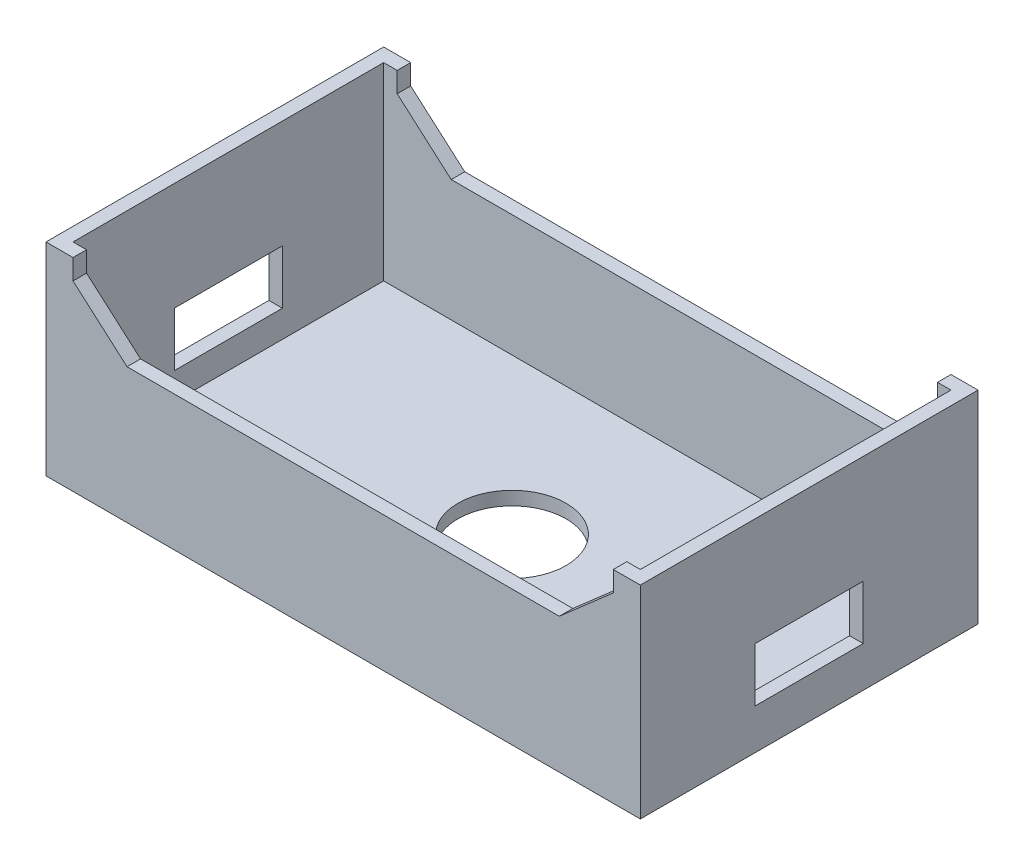
SolidWorks part; units mm, degrees
material "ABS"
ref_plane "Alzado" through (0, 0, 0) normal (0, 0, 1) x (1, 0, 0)
ref_plane "Planta" through (0, 0, 0) normal (0, 1, 0) x (1, 0, 0)
ref_plane "Vista lateral" through (0, 0, 0) normal (1, 0, 0) x (0, 0, -1)
sketch "Croquis1" plane through (0, 0, 0) normal (0, 1, 0) x (1, 0, 0)
  line L1 (22, -12.5) -> (-22, -12.5)
  line L2 (22, -12.5) -> (22, 12.5)
  line L3 (22, 12.5) -> (-22, 12.5)
  line L4 (-22, -12.5) -> (-22, 12.5)
  line L5 (22, -12.5) -> (-22, 12.5) construction
  line L6 (22, 12.5) -> (-22, -12.5) construction
  point P0 (0, 0)
  dimension "D1" = 25
  dimension "D2" = 44
extrude "Saliente-Extruir2" add sketch "Croquis1" along normal blind 10
sketch "Croquis2" plane through (0, 10, 0) normal (0, 1, 0) x (1, 0, 0)
  line L0 (22, 12.5) -> (-22, 12.5) construction
  line L1 (21, -11.5) -> (-21, -11.5)
  line L2 (21, -11.5) -> (21, 11.5)
  line L3 (21, 11.5) -> (-21, 11.5)
  line L4 (-21, -11.5) -> (-21, 11.5)
  line L5 (21, -11.5) -> (-21, 11.5) construction
  line L6 (21, 11.5) -> (-21, -11.5) construction
  line L7 (-22, 12.5) -> (-22, -12.5) construction
  point P0 (0, 0)
  dimension "D1" = 1
  dimension "D2" = 1
extrude "Cortar-Extruir1" cut sketch "Croquis2" against normal blind 9
sketch "Croquis3" plane through (0, 0, 12.5) normal (0, 0, 1) x (1, 0, 0)
  line L0 (0, 10) -> (0, 15.8262)
  line L1 (-22, 10) -> (22, 10) construction
  line L2 (-22, 10) -> (-23, 10)
  line L3 (-22, 10) -> (-22, 0) construction
  line L4 (-23, 10) -> (-23, 15)
  line L5 (-23, 15) -> (-20, 15)
  line L6 (-20, 15) -> (-20, 13.5)
  line L7 (-23, 10) -> (-16, 10)
  line L8 (-16, 10) -> (-20, 13.5)
  line L9 (16, 10) -> (20, 13.5)
  line L10 (23, 10) -> (16, 10)
  line L11 (20, 15) -> (20, 13.5)
  line L12 (23, 10) -> (23, 15)
  line L13 (22, 10) -> (23, 10)
  line L14 (-23, 10) -> (-23, 8)
  line L15 (-23, 8) -> (-22, 8)
  line L16 (-22, 8) -> (-22, 10)
  line L17 (22, 8) -> (22, 10)
  line L18 (23, 8) -> (22, 8)
  line L19 (23, 10) -> (23, 8)
  line L20 (22, 10) -> (23, 10)
  line L21 (20, 15) -> (23, 15)
  line M2 (22, 0) -> (22, 10)
  line M3 (22, 10) -> (-22, 10)
  line M4 (-22, 10) -> (-22, 0)
extrude "Saliente-Extruir3" add sketch "Croquis3" against normal blind 25 contours L8 L6 L5 L4 L2 M3 | L21 L11 L9 L10 L12 M3 | L14 L15 L2 M4 | L19 L10 L18 M2 region at (-22.5, 9, 12.5) region at (-20.5985, 12.0758, 12.5) region at (20.5985, 12.0758, 12.5) region at (22.5, 9, 12.5)
sketch "Croquis4" plane through (0, 1, 0) normal (0, 1, 0) x (1, 0, 0)
  line L0 (21, 11.5) -> (-21, 11.5) construction
  line L1 (21, -11.5) -> (-21, -11.5)
  line L2 (21, -11.5) -> (21, 11.5)
  line L3 (21, 11.5) -> (-21, 11.5)
  line L4 (-21, -11.5) -> (-21, 11.5)
  line L5 (21, -11.5) -> (-21, 11.5) construction
  line L6 (21, 11.5) -> (-21, -11.5) construction
  point P0 (0, 0)
extrude "Cortar-Extruir2" cut sketch "Croquis4" along normal blind 28
sketch "Croquis5" plane through (0, 15, 0) normal (0, 1, 0) x (1, 0, 0)
  line L0 (-23, 12.5) -> (-21, -12.5)
  line L1 (-23, -12.5) -> (-20, -12.5) construction
  line L2 (-23, 12.5) -> (-22, 12.5)
  line L3 (-22, 12.5) -> (-21, 12.5)
  line L4 (-23, 12.5) -> (-20, 12.5) construction
  line L5 (0, 0) -> (0, -16.8215)
  line L6 (-22, 12.5) -> (-21, 12.5)
  line L7 (-22, 12.5) -> (-22, -12.5)
  line L8 (-22, -12.5) -> (-21, -12.5)
  line L9 (-21, 12.5) -> (-21, -12.5)
  line L10 (21, 12.5) -> (21, -12.5)
  line L11 (22, -12.5) -> (21, -12.5)
  line L12 (22, 12.5) -> (22, -12.5)
  line L13 (22, 12.5) -> (21, 12.5)
  line L14 (22, 12.5) -> (21, 12.5)
  line L15 (23, 12.5) -> (22, 12.5)
  line L16 (23, 12.5) -> (21, -12.5)
  line L17 (21, -11.5) -> (22, -11.5)
  line L19 (21, 11.5) -> (22, 11.5)
  line L20 (21, 11.5) -> (21, -11.5)
  line L21 (21, -11.5) -> (22, -11.5)
  line L22 (22, 11.5) -> (22, -11.5)
  line L23 (-21, 11.5) -> (-22, 11.5)
  line L24 (-21, 11.5) -> (-21, -11.5)
  line L25 (-21, -11.5) -> (-22, -11.5)
  line L26 (-22, 11.5) -> (-22, -11.5)
extrude "Cortar-Extruir10" cut sketch "Croquis5" against normal blind 5 contours L25 L5 L23 L7 L0 | L25 L0 L7 | L19 L10 L17 L16 L12 | L16 L17 L12 region at (-21.4423, 15, -2.29) region at (-21.6933, 15, 7.6667) region at (21.4423, 15, -2.29) region at (21.6933, 15, 7.6667)
sketch "Croquis6" plane through (23, 0, 0) normal (1, 0, 0) x (0, 0, -1)
  line L1 (-15.4714, 16.8377) -> (14.422, 16.8377)
  line L2 (-15.4714, 16.8377) -> (-15.4714, 5.3904)
  line L3 (-15.4714, 5.3904) -> (14.422, 5.3904)
  line L4 (14.422, 16.8377) -> (14.422, 5.3904)
extrude "Cortar-Extruir11" cut sketch "Croquis6" against normal blind 1
sketch "Croquis7" plane through (-23, 0, 0) normal (-1, 0, 0) x (0, 0, 1)
  line L1 (-16.2316, 17.1898) -> (14.7722, 17.1898)
  line L2 (-16.2316, 17.1898) -> (-16.2316, 7.3211)
  line L3 (-16.2316, 7.3211) -> (14.7722, 7.3211)
  line L4 (14.7722, 17.1898) -> (14.7722, 7.3211)
extrude "Cortar-Extruir12" cut sketch "Croquis7" against normal blind 1
sketch "Croquis8" plane through (0, 10, 0) normal (0, 1, 0) x (1, 0, 0)
  line L0 (0, 0) -> (0, 8.9095)
  line L1 (-21, -11.5) -> (-22, -11.5)
  line L2 (-21, -11.5) -> (-21, 11.5)
  line L3 (-21, 11.5) -> (-22, 11.5)
  line L4 (-22, -11.5) -> (-22, 11.5)
  line L5 (22, -11.5) -> (22, 11.5)
  line L6 (21, 11.5) -> (22, 11.5)
  line L7 (21, -11.5) -> (21, 11.5)
  line L8 (21, -11.5) -> (22, -11.5)
  line M1 (-22, -11.5) -> (-21, -11.5)
  line M2 (-21, -11.5) -> (-21, 11.5)
  line M3 (-21, 11.5) -> (-22, 11.5)
  line M4 (-22, 11.5) -> (-22, -11.5)
extrude "Saliente-Extruir4" add sketch "Croquis8" along normal blind 5 contours M4 M1 M2 M3 | L7 L8 L5 L6 region at (-21.5, 10, 0) region at (21.5, 10, 0)
sketch "Croquis9" plane through (-22, 0, 0) normal (-1, 0, 0) x (0, 0, 1)
  line L0 (12.5, 15) -> (-12.5, 15) construction
  line L1 (-4, 7) -> (4, 7)
  line L2 (-4, 7) -> (-4, 3)
  line L3 (-4, 3) -> (4, 3)
  line L4 (4, 7) -> (4, 3)
  line L5 (-4, 7) -> (4, 3) construction
  line L6 (-4, 3) -> (4, 7) construction
  line L7 (-12.5, 0) -> (12.5, 0) construction
  line L8 (-12.5, 15) -> (-12.5, 0) construction
  point P0 (0, 5)
  dimension "D1" = 8
  dimension "D2" = 4
  dimension "D3" = 8
  dimension "D4" = 8.5
extrude "Cortar-Extruir17" cut sketch "Croquis9" against normal blind 87
sketch "Croquis10" plane through (0, 0, 0) normal (0, -1, 0) x (1, 0, 0)
  circle A0 centre (0, 0) radius 4
extrude "Cortar-Extruir19" cut sketch "Croquis10" against normal blind 10
